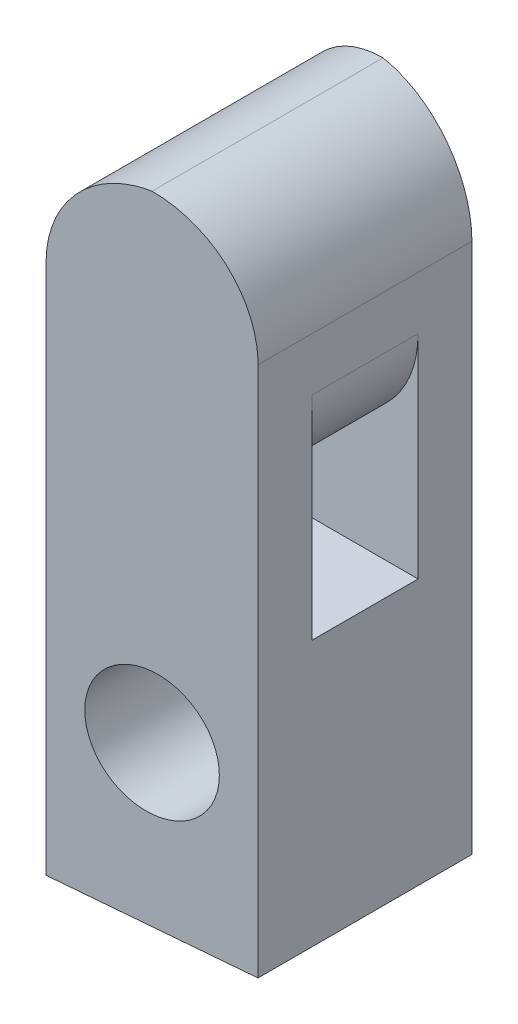
SolidWorks part; units mm, degrees
ref_plane "Front Plane" through (0, 0, 0) normal (0, 0, 1) x (1, 0, 0)
ref_plane "Top Plane" through (0, 0, 0) normal (0, 1, 0) x (1, 0, 0)
ref_plane "Right Plane" through (0, 0, 0) normal (1, 0, 0) x (0, 0, -1)
sketch "Sketch2" plane through (0, 0, 0) normal (0, 1, 0) x (1, 0, 0)
  line L0 (-1.835, -2.335) -> (1.835, -2.335) construction
  line L1 (-1.835, -2.335) -> (-1.835, 2.335)
  line L2 (1.835, -2.335) -> (1.835, 2.335) construction
  line L3 (-1.835, 2.335) -> (1.835, 2.335) construction
  line L4 (-1.835, -2.335) -> (1.835, 2.335) construction
  line L5 (1.835, -2.335) -> (-1.835, 2.335) construction
  line L6 (-1.835, 2.335) -> (1.835, 2.0139)
  line L7 (-1.835, -2.335) -> (1.835, -2.0139)
  line L8 (1.835, -2.0139) -> (1.835, 2.0139)
  point P1 (0, 0)
  dimension "D1" = 5
  dimension "D2" = 5
  dimension "D3" = 4.67
  dimension "D4" = 3.67
extrude "Boss-Extrude1" add sketch "Sketch2" along normal blind 10
sketch "Sketch3" plane through (0, 10, 0) normal (0, 1, 0) x (1, 0, 0)
  line L4 (1.835, -2.0139) -> (1.835, 2.0139)
  line L5 (1.835, 2.0139) -> (-1.835, 2.335)
  line L6 (-1.835, 2.335) -> (-1.835, -2.335)
  line L7 (-1.835, -2.335) -> (1.835, -2.0139)
  line L8 (1.835, -2.0139) -> (1.835, 2.0139)
  line L9 (1.835, 2.0139) -> (-1.835, 2.335)
  line L10 (-1.835, 2.335) -> (-1.835, -2.335)
  line L11 (-1.835, -2.335) -> (1.835, -2.0139)
  dimension "D1" = 0
extrude "Boss-Extrude2" add sketch "Sketch3" along normal blind 2
sketch "Sketch4" plane through (1.835, 0, 0) normal (1, 0, 0) x (0, 0, -1)
  line L0 (0, 0) -> (0, 12) construction
  line L1 (-2.0139, 12) -> (2.0139, 12) construction
  line L3 (-1, 5) -> (1, 5)
  line L4 (-1, 5) -> (-1, 7)
  line L5 (-1, 7) -> (1, 7)
  line L6 (1, 5) -> (1, 7)
  line L7 (-1, 5) -> (1, 7) construction
  line L8 (-1, 7) -> (1, 5) construction
  point P5 (0, 6)
  dimension "D1" = 2
  dimension "D2" = 2
extrude "Cut-Extrude1" cut sketch "Sketch4" against normal up to surface (3.67 mm away) up to face at (-1.835, 6, 0)
fillet "Fillet1" radius 2 4 edges at (1.835, 12, 0) (-1.835, 12, 0) (-1.835, 7, 0) (1.835, 7, 0)
sketch "Sketch6" plane through (0, 0, 0) normal (0, 0, 1) x (1, 0, 0)
  line L0 (0, 0) -> (0, 3) construction
  circle A0 centre (0, 3) radius 1.165
  dimension "D2" = 2.33
  dimension "D1" = 3
extrude "Cut-Extrude2" cut sketch "Sketch6" against normal through all both and the other way through all
equation "\"chuck_width\"=5"
equation "\"D3@Sketch2\"=\"chuck_width\"-\"tol\""
equation "\"chuck_length\" = 4"
equation "\"D4@Sketch2\"=\"chuck_length\"-\"tol\""
equation "\"chuck_angle\"=5"
equation "\"D2@Sketch2\"=\"chuck_angle\""
equation "\"D1@Sketch2\"=\"chuck_angle\""
equation "\"chuck_depth\"=10"
equation "\"chuck_height\"= 2"
equation "\"pin_offset\"=3"
equation "\"D1@Sketch6\"=\"pin_offset\""
equation "\"pin_dia\"=2"
equation "\"D2@Sketch6\"=\"pin_dia\"+\"tol\""
equation "\"tol\"= 0.33"
